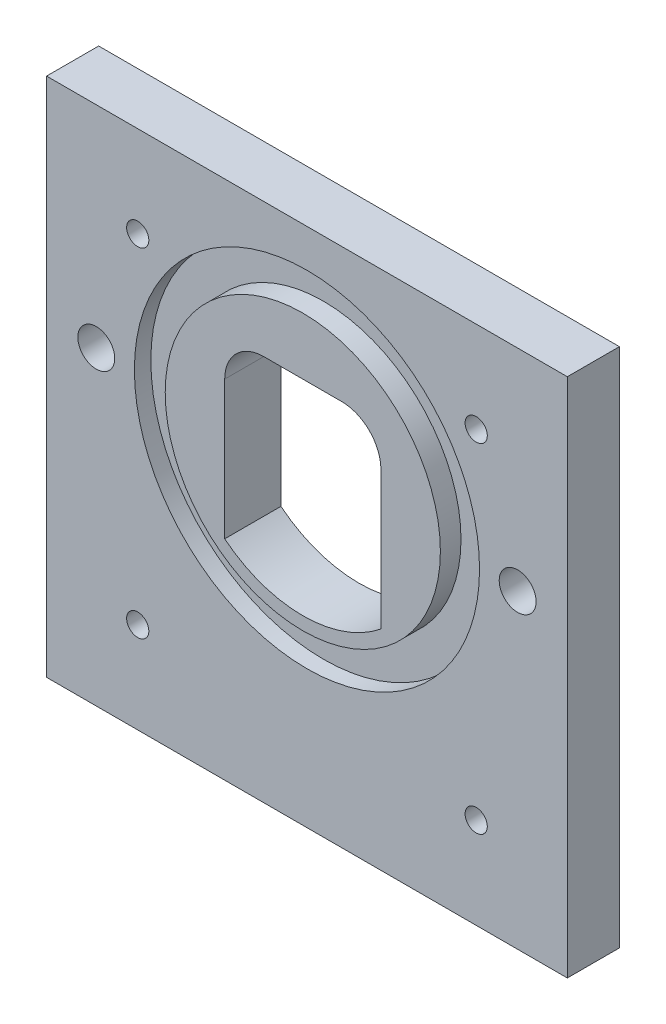
SolidWorks part; units mm, degrees
ref_plane "Front Plane" through (0, 0, 0) normal (0, 0, 1) x (1, 0, 0)
ref_plane "Top Plane" through (0, 0, 0) normal (0, 1, 0) x (1, 0, 0)
ref_plane "Right Plane" through (0, 0, 0) normal (1, 0, 0) x (0, 0, -1)
sketch "Sketch1" plane through (0, 0, 0) normal (0, 0, 1) x (1, 0, 0)
  line L1 (-31.75, -31.75) -> (31.75, -31.75)
  line L2 (-31.75, -31.75) -> (-31.75, 31.75)
  line L3 (-31.75, 31.75) -> (31.75, 31.75)
  line L4 (31.75, -31.75) -> (31.75, 31.75)
  line L5 (-31.75, -31.75) -> (31.75, 31.75) construction
  line L6 (-31.75, 31.75) -> (31.75, -31.75) construction
  point P0 (0, 0)
  dimension "D1" = 63.5
  dimension "D2" = 63.5
extrude "Boss-Extrude1" add sketch "Sketch1" along normal blind 6.35
hole_wizard "#6-32 Tapped Hole1" positions "Sketch3" profile "Sketch2" tap size "#6-32" standard "Ansi Inch" end condition through all
sketch "Sketch3" plane through (0, 0, 0) normal (0, 0, -1) x (-1, 0, 0)
  point P1 (20.6375, -20.6375)
  point P4 (-20.6375, -20.6375)
  point P7 (-20.6375, 20.6375)
  point P10 (20.6375, 20.6375)
sketch "Sketch2" plane through (-20.6375, -20.6375, 0) normal (1, 0, 0) x (0, 1, 0)
  line L0 (0, 0) -> (0, 6.35)
  line L1 (0, 6.35) -> (1.3525, 6.35)
  line L2 (1.3525, 6.35) -> (1.3525, 0)
  line L5 (1.3525, 0) -> (0, 0)
  line L11 (0, -6.35) -> (0, 107.95) construction
  dimension "Thread Major Dia." = 2.7051
  dimension "Thru Tap Drill Depth" = 6.35
sketch "Sketch4" plane through (0, 0, 6.35) normal (0, 0, 1) x (1, 0, 0)
  circle A0 centre (0, 6.0769) radius 21.0439
  circle A1 centre (0, 6.0769) radius 16.7767
  dimension "D1" = 33.5534
  dimension "D2" = 42.0878
extrude "Cut-Extrude1" cut sketch "Sketch4" against normal blind 2.0066
sketch "Sketch5" plane through (0, 0, 6.35) normal (0, 0, 1) x (1, 0, 0)
  circle A0 centre (0, 6.0769) radius 16.7767
extrude "Boss-Extrude2" add sketch "Sketch5" along normal blind 0.508
hole_wizard "CSK for M4 Flat Head Machine Screw1" positions "Sketch7" profile "Sketch6" countersink size "M4" standard "Ansi Metric" end condition through all
sketch "Sketch7" plane through (0, 0, 0) normal (0, 0, -1) x (-1, 0, 0)
  point P1 (-25.6912, 6.0769)
  point P4 (25.6912, 6.0769)
sketch "Sketch6" plane through (25.6912, 6.0769, 0) normal (1, 0, 0) x (0, 1, 0)
  line L0 (0, 0) -> (0, 6.858)
  line L1 (0, 6.858) -> (2.25, 6.858)
  line L2 (2.25, 6.858) -> (2.25, 2.45)
  line L3 (2.25, 2.45) -> (4.7, 0)
  line L5 (4.7, 0) -> (0, 0)
  line L6 (-2.25, 2.45) -> (-4.7, 0) construction
  line L11 (0, -6.35) -> (0, 107.95) construction
  dimension "Thru Hole Dia." = 4.5
  dimension "Thru Hole Depth" = 6.858
  dimension "Near C'Sink Dia." = 9.4
  dimension "Near C'Sink Angle" = 90
sketch "Sketch9" plane through (0, 0, 0) normal (0, 0, -1) x (-1, 0, 0)
  line L0 (9.525, 11.1125) -> (9.525, -5.7547)
  line L1 (9.525, -11.1125) -> (9.525, 11.1125) construction
  line L2 (4.7625, 15.875) -> (-4.7625, 15.875)
  line L3 (0, 7.7056) -> (0, -1.8816) construction
  line L4 (-9.525, 11.1125) -> (-9.525, -5.7547)
  circle A0 centre (0, 6.0769) radius 15.1892 construction
  circle A1 centre (0, 6.0769) radius 16.7767 construction
  arc A2 (9.525, 11.1125) -> (4.7625, 15.875) centre (4.7625, 11.1125) ccw
  arc A3 (-9.525, -5.7547) -> (9.525, -5.7547) centre (0, 6.0769) ccw
  arc A4 (-9.525, 11.1125) -> (-4.7625, 15.875) centre (-4.7625, 11.1125) cw
  point P19 (0, 15.875)
  dimension "D1" = 1.5875
extrude "Cut-Extrude2" cut sketch "Sketch9" against normal through all
ref_point "Point1"
